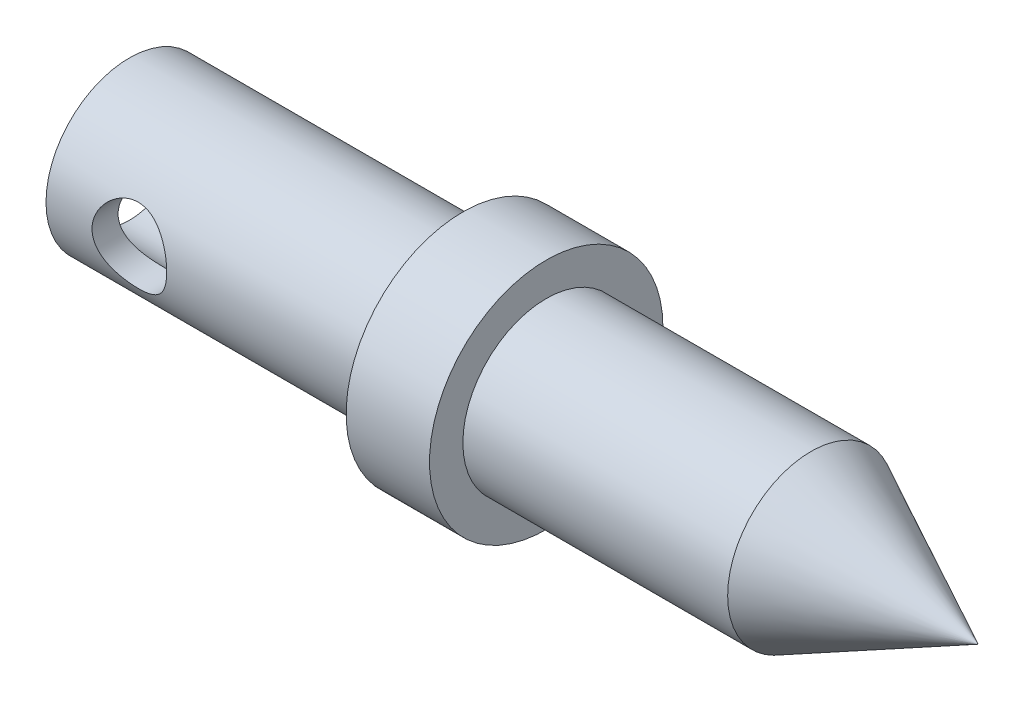
SolidWorks part; units mm, degrees
ref_plane "Front Plane" through (0, 0, 0) normal (0, 0, 1) x (1, 0, 0)
ref_plane "Top Plane" through (0, 0, 0) normal (0, 1, 0) x (1, 0, 0)
ref_plane "Right Plane" through (0, 0, 0) normal (1, 0, 0) x (0, 0, -1)
sketch "Sketch1" plane through (0, 0, 0) normal (1, 0, 0) x (0, 0, -1)
  circle A0 centre (0, 0) radius 4.445
  dimension "D1" = 8.89
extrude "Boss-Extrude1" add sketch "Sketch1" along normal blind 3.175
sketch "Sketch2" plane through (3.175, 0, 0) normal (1, 0, 0) x (0, 0, -1)
  circle A0 centre (0, 0) radius 3.175
  dimension "D1" = 6.35
extrude "Boss-Extrude2" add sketch "Sketch2" along normal blind 16.4338
sketch "Sketch3" plane through (0, 0, 0) normal (-1, 0, 0) x (0, 0, 1)
  circle A0 centre (0, 0) radius 3.175
  dimension "D1" = 6.35
extrude "Boss-Extrude3" add sketch "Sketch3" along normal blind 12.7
chamfer "Chamfer1" distance 6.35 angle 26.5 1 edges at (19.6088, 0, -3.175) first distance on face at (19.6088, 0, -3.175)
sketch "Sketch4" plane through (-12.7, 0, 0) normal (-1, 0, 0) x (0, 0, 1)
  circle A0 centre (0, 0) radius 2.1828
  point P0 (0, 0)
  dimension "D1" = 4.3656
extrude "Cut-Extrude1" cut sketch "Sketch4" against normal blind 6.35 contours A0
sketch "Sketch5" plane through (-6.35, 0, 0) normal (-1, 0, 0) x (0, 0, 1)
  circle A0 centre (0, 0) radius 1.7859
  dimension "D1" = 3.5719
extrude "Cut-Extrude2" cut sketch "Sketch5" against normal blind 1.905
ref_axis "Axis1" through (10.5528, 0, 0) along (-1, 0, 0)
sketch "Sketch7" plane through (0, 0, 0) normal (0, 0, 1) x (1, 0, 0)
  line L0 (10.5528, 0) -> (-32.6021, 0) construction
  line L1 (-12.7, 2.1828) -> (-12.7, -2.1828) construction
  circle A0 centre (-9.525, 0) radius 1.4224
  point P0 (-9.525, 0)
  dimension "D2" = 2.8448
  dimension "D1" = 3.175
extrude "Cut-Extrude5" cut sketch "Sketch7" along normal up to surface and the other way through all contours A0 up to face at (-12.7, 0, 3.175)
ref_axis "Axis2" through (-9.525, 0, 3.175) along (0, 0, -1)
ref_plane "Plane2" through (0, 0, 3.175) normal (0, 0, 1) x (1, 0, 0)
ref_axis "Axis3" through (-9.525, 0, 4.5207) along (0, 0, -1)
ref_plane "Plane3" through (-9.525, 0, 0) normal (-1, 0, 0) x (0, 0, 1)
ref_plane "Plane4" through (-8.1026, 0, 0) normal (-1, 0, 0) x (0, 0, 1)
